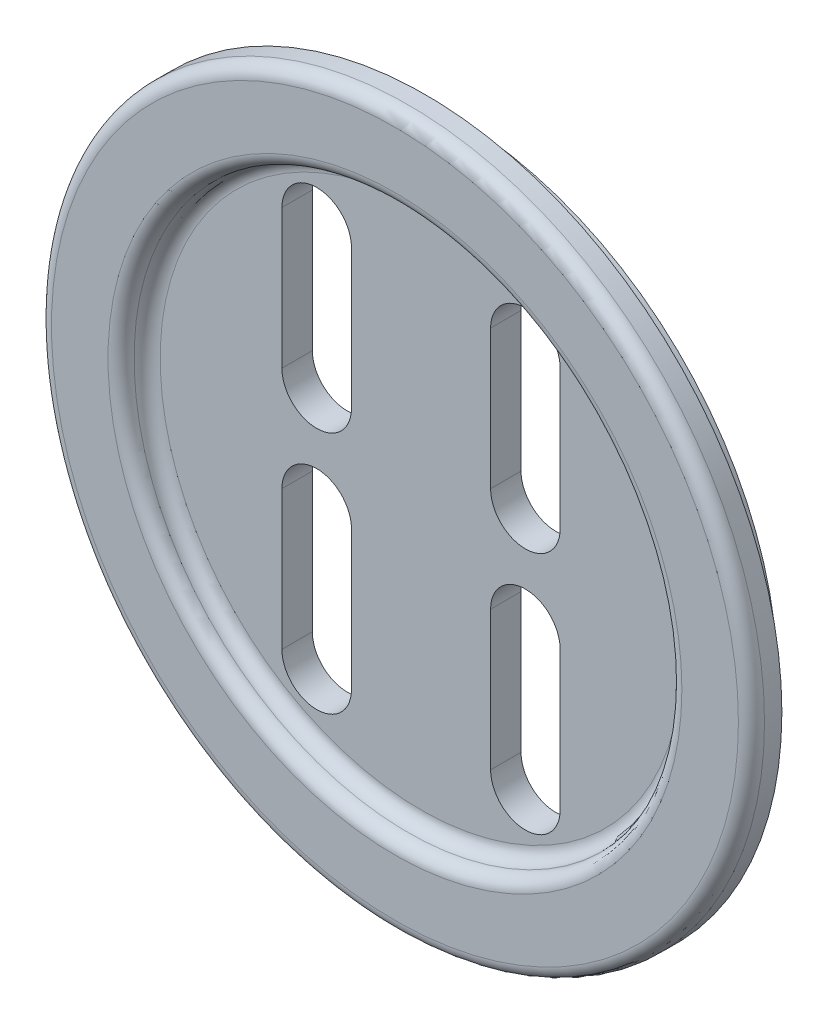
SolidWorks part; units mm, degrees
material "2014 Alloy"
ref_plane "Front Plane" through (0, 0, 0) normal (0, 0, 1) x (1, 0, 0)
ref_plane "Top Plane" through (0, 0, 0) normal (0, 1, 0) x (1, 0, 0)
ref_plane "Right Plane" through (0, 0, 0) normal (1, 0, 0) x (0, 0, -1)
sketch "Sketch1" plane through (0, 0, 0) normal (0, 0, 1) x (1, 0, 0)
  circle A0 centre (0, 0) radius 41
  dimension "D1" = 82
extrude "Boss-Extrude1" add sketch "Sketch1" along normal blind 3.5
sketch "Sketch2" plane through (0, 0, 0) normal (0, 0, 1) x (1, 0, 0)
  circle A0 centre (0, 0) radius 37.5
  dimension "D1" = 75
extrude "Boss-Extrude2" add sketch "Sketch2" against normal blind 3
ref_plane "Plane1" through (0, 0, 3.5) normal (0, 0, 1) x (1, 0, 0)
sketch "Sketch4" plane through (0, 0, 3.5) normal (0, 0, 1) x (1, 0, 0)
  circle A0 centre (0, 0) radius 31.5
  dimension "D1" = 63
extrude "Cut-Extrude3" cut sketch "Sketch4" against normal blind 3
sketch "Sketch5" plane through (0, 0, 3.5) normal (0, 0, 1) x (1, 0, 0)
  line L0 (0, 31.5) -> (0, -31.5) construction
  line L1 (-12, 22) -> (-12, 6)
  line L2 (-16, 22) -> (-16, 6)
  line L3 (-8, 22) -> (-8, 6)
  line L4 (0, 0) -> (-31.5, 0) construction
  line L5 (-8, -22) -> (-8, -6)
  line L6 (-16, -22) -> (-16, -6)
  line L7 (16, -22) -> (16, -6)
  line L8 (8, -22) -> (8, -6)
  line L9 (16, 22) -> (16, 6)
  line L10 (8, 22) -> (8, 6)
  circle A0 centre (0, 0) radius 31.5 construction
  circle A1 centre (0, 0) radius 31.5 construction
  arc A2 (-16, 22) -> (-8, 22) centre (-12, 22) cw
  arc A3 (-16, 6) -> (-8, 6) centre (-12, 6) ccw
  arc A4 (-16, -6) -> (-8, -6) centre (-12, -6) cw
  arc A5 (-16, -22) -> (-8, -22) centre (-12, -22) ccw
  arc A6 (16, -22) -> (8, -22) centre (12, -22) cw
  arc A7 (16, -6) -> (8, -6) centre (12, -6) ccw
  arc A8 (16, 6) -> (8, 6) centre (12, 6) cw
  arc A9 (16, 22) -> (8, 22) centre (12, 22) ccw
  dimension "D1" = 16
  dimension "D2" = 12
  dimension "D3" = 6
  dimension "D4" = 4
  dimension "D5" = 4
extrude "Cut-Extrude4" cut sketch "Sketch5" against normal blind 21 contours L2 A3 L3 A2 | L10 A8 L9 A9 | L6 A4 L5 A5 | L8 A7 L7 A6
fillet "Fillet1" radius 1.5 3 edges at (31.5, 0, 0.5) (31.5, 0, 3.5) (41, 0, 3.5)
